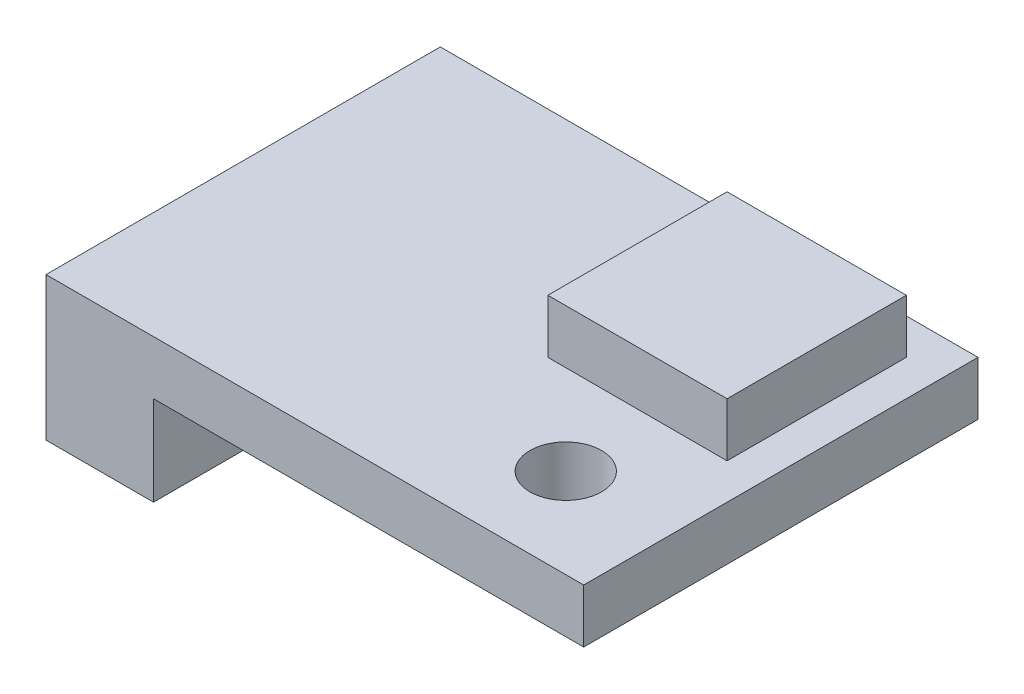
SolidWorks part; units mm, degrees
ref_plane "Спереди" through (0, 0, 0) normal (0, 0, 1) x (1, 0, 0)
ref_plane "Сверху" through (0, 0, 0) normal (0, 1, 0) x (1, 0, 0)
ref_plane "Справа" through (0, 0, 0) normal (1, 0, 0) x (0, 0, -1)
sketch "Эскиз1" plane through (0, 0, 0) normal (0, 1, 0) x (1, 0, 0)
  line L1 (7.5, 5.5) -> (-7.5, 5.5)
  line L2 (7.5, 5.5) -> (7.5, -5.5)
  line L3 (7.5, -5.5) -> (-7.5, -5.5)
  line L4 (-7.5, 5.5) -> (-7.5, -5.5)
  line L5 (7.5, 5.5) -> (-7.5, -5.5) construction
  line L6 (7.5, -5.5) -> (-7.5, 5.5) construction
  line L7 (7.5, 5.5) -> (6.5, 5.5) construction
  line L8 (7.5, 5.5) -> (7.5, 4.5) construction
  line L9 (7.5, 4.5) -> (6.5, 4.5) construction
  line L10 (6.5, 5.5) -> (6.5, 4.5) construction
  line L11 (6.5, 4.5) -> (1.5, 4.5)
  line L12 (6.5, 4.5) -> (6.5, -0.5)
  line L13 (6.5, -0.5) -> (1.5, -0.5)
  line L14 (1.5, 4.5) -> (1.5, -0.5)
  line L15 (-7.5, 5.5) -> (-4.5, 5.5)
  line L16 (-7.5, 5.5) -> (-7.5, -5.5)
  line L17 (-7.5, -5.5) -> (-4.5, -5.5)
  line L18 (-4.5, 5.5) -> (-4.5, -5.5)
  line L19 (7.5, -5.5) -> (4.5, -5.5)
  line L20 (7.5, -5.5) -> (7.5, -3)
  line L21 (7.5, -3) -> (4.5, -3) construction
  line L22 (4.5, -5.5) -> (4.5, -3) construction
  circle A0 centre (4.5, -3) radius 1
  point P0 (0, 0)
  dimension "D9" = 2
  dimension "D1" = 15
  dimension "D2" = 11
  dimension "D3" = 1
  dimension "D4" = 1
  dimension "D5" = 5
  dimension "D6" = 3
  dimension "D7" = 3
  dimension "D8" = 2.5
extrude "Бобышка-Вытянуть1" add sketch "Эскиз1" along normal blind 1.5 contours L18 L1 L4 L3 | L1 L18 L3 L2 L14 L11 L12 L13 | L11 L14 L13 L12 region at (0.8075, 0, 0.3907) region at (-6, 0, 0) region at (4, 0, -2)
extrude "Бобышка-Вытянуть2" add sketch "Эскиз1<3>" against normal blind 2.5 contours L18 L1 L4 L3 region at (-6, 0, 0)
sketch "Эскиз1<3>" plane through (0, 0, 0) normal (0, 1, 0) x (1, 0, 0) same geometry as "Эскиз1"
extrude "Бобышка-Вытянуть3" add sketch "Эскиз1<4>" along normal blind 1.5 from surface contours L11 L14 L13 L12 region at (4, 0, -2) starting at face at (0, 1.5, 0)
sketch "Эскиз1<4>" plane through (0, 0, 0) normal (0, 1, 0) x (1, 0, 0) same geometry as "Эскиз1"
